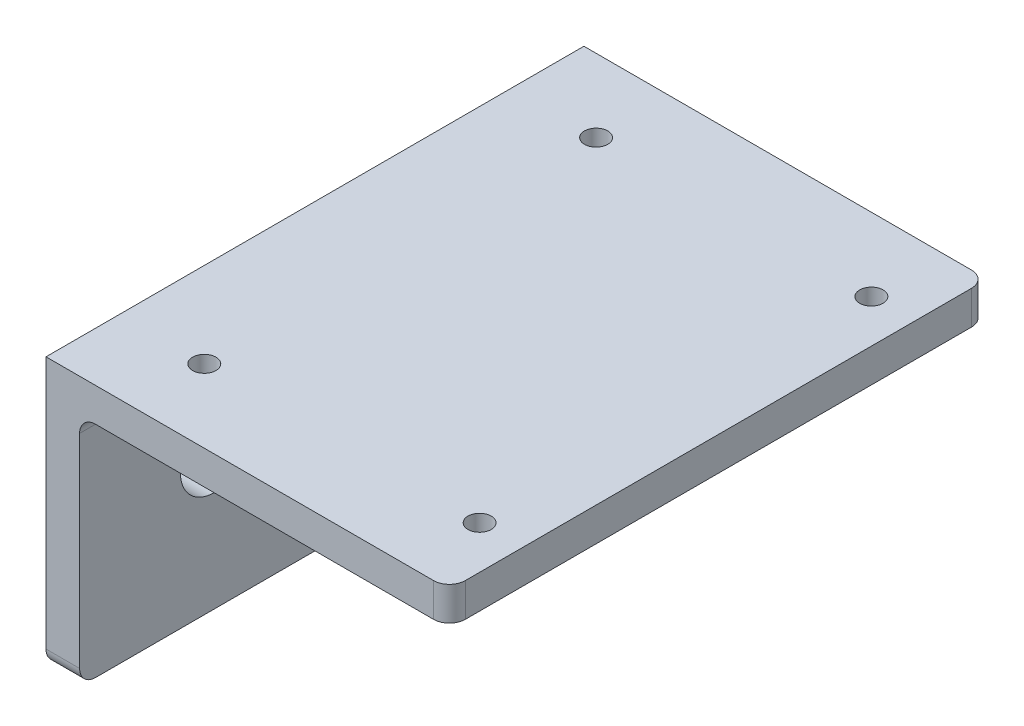
SolidWorks part; units mm, degrees
material "ABS"
ref_plane "Front Plane" through (0, 0, 0) normal (0, 0, 1) x (1, 0, 0)
ref_plane "Top Plane" through (0, 0, 0) normal (0, 1, 0) x (1, 0, 0)
ref_plane "Right Plane" through (0, 0, 0) normal (1, 0, 0) x (0, 0, -1)
sketch "Sketch2" plane through (0, 0, 0) normal (1, 0, 0) x (0, 0, -1)
  line L1 (-25.4, -12.7) -> (25.4, -12.7)
  line L2 (-25.4, -12.7) -> (-25.4, 12.7)
  line L3 (-25.4, 12.7) -> (25.4, 12.7)
  line L4 (25.4, -12.7) -> (25.4, 12.7)
  line L5 (-25.4, -12.7) -> (25.4, 12.7) construction
  line L6 (-25.4, 12.7) -> (25.4, -12.7) construction
  point P0 (0, 0)
  dimension "D1" = 25.4
  dimension "D2" = 50.8
extrude "Boss-Extrude1" add sketch "Sketch2" along normal blind 3.175
sketch "Sketch4" plane through (0, 12.7, 0) normal (0, 1, 0) x (1, 0, 0)
  line L1 (0, 25.4) -> (38.1, 25.4)
  line L2 (0, 25.4) -> (0, -25.4)
  line L3 (0, -25.4) -> (38.1, -25.4)
  line L4 (38.1, 25.4) -> (38.1, -25.4)
  dimension "D1" = 50.8
  dimension "D2" = 38.1
extrude "Boss-Extrude2" add sketch "Sketch4" against normal blind 3.175
sketch "Sketch5" plane through (0, 12.7, 0) normal (0, 1, 0) x (1, 0, 0)
  line L0 (19.05, 0) -> (21.05, 0) construction
  line L1 (8.05, -18.5) -> (34.05, -18.5) construction
  line L2 (8.05, -18.5) -> (8.05, 18.5) construction
  line L3 (8.05, 18.5) -> (34.05, 18.5) construction
  line L4 (34.05, -18.5) -> (34.05, 18.5) construction
  line L5 (8.05, -18.5) -> (34.05, 18.5) construction
  line L6 (8.05, 18.5) -> (34.05, -18.5) construction
  circle A0 centre (8.05, 18.5) radius 1.1
  circle A1 centre (34.05, 18.5) radius 1.1
  circle A2 centre (34.05, -18.5) radius 1.1
  circle A3 centre (8.05, -18.5) radius 1.1
  point P0 (21.05, 0)
  dimension "D1" = 26
  dimension "D2" = 37
extrude "Cut-Extrude1" cut sketch "Sketch5" against normal blind 3.175
sketch "Sketch6" plane through (0, 0, 0) normal (-1, 0, 0) x (0, 0, 1)
  line L0 (12.7, 0) -> (-12.7, 0) construction
  circle A0 centre (-12.7, 0) radius 3.175
  circle A1 centre (12.7, 0) radius 3.175
  point P4 (0, 0)
extrude "Cut-Extrude2" cut sketch "Sketch6" against normal blind 3.175
sketch "Sketch7" plane through (0, 0, 0) normal (0, 0, 1) x (1, 0, 0)
  line L2 (3.175, -12.7) -> (25.4, 9.525)
  line L3 (3.175, 9.525) -> (38.1, 9.525) construction
  line L8 (3.175, -12.7) -> (3.175, 9.525)
  line L9 (25.4, 9.525) -> (3.175, 9.525)
extrude "Boss-Extrude3" add sketch "Sketch7" along normal mid plane 3.175
fillet "Fillet3" radius 1.5 11 edges at (3.175, -1.5875, -1.5875) (14.2875, 9.525, -1.5875) (25.4, 9.525, 0) (3.175, -1.5875, 1.5875) (14.2875, 9.525, 1.5875) (3.175, 9.525, 13.4937) (3.175, 9.525, -13.4937) (1.5875, -12.7, 25.4) (1.5875, -12.7, -25.4) (38.1, 11.1125, 25.4) (38.1, 11.1125, -25.4)
